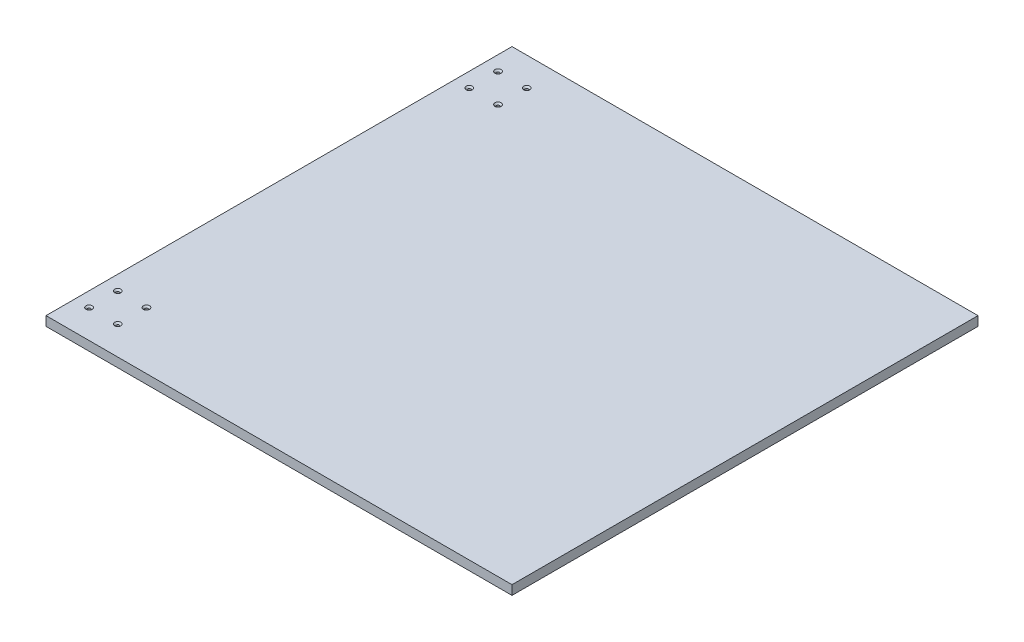
SolidWorks part; units mm, degrees
material "Buk"
ref_plane "Płaszczyzna przednia" through (0, 0, 0) normal (0, 0, 1) x (1, 0, 0)
ref_plane "Płaszczyzna górna" through (0, 0, 0) normal (0, 1, 0) x (1, 0, 0)
ref_plane "Płaszczyzna prawa" through (0, 0, 0) normal (1, 0, 0) x (0, 0, -1)
sketch "Szkic1" plane through (0, 0, 0) normal (0, 1, 0) x (1, 0, 0)
  line L1 (0, 0) -> (500, 0)
  line L2 (0, 0) -> (0, 500)
  line L3 (0, 500) -> (500, 500)
  line L4 (500, 0) -> (500, 500)
  dimension "D1" = 500
extrude "Dodanie-wyciągnięcie1" add sketch "Szkic1" along normal blind 10
sketch "Szkic2" plane through (0, 10, 0) normal (0, 1, 0) x (1, 0, 0)
  line L0 (0, 0) -> (500, 0) construction
  line L1 (0, 500) -> (0, 0) construction
  line L2 (0, 250) -> (500, 250) construction
  line L3 (500, 0) -> (500, 500) construction
  circle A0 centre (15.6, 30.6) radius 1.6
  circle A1 centre (15.6, 61.4) radius 1.6
  circle A2 centre (46.4, 61.4) radius 1.6
  circle A3 centre (46.4, 30.6) radius 1.6
  circle A4 centre (15.6, 438.6) radius 1.6
  circle A5 centre (15.6, 469.4) radius 1.6
  circle A6 centre (46.4, 469.4) radius 1.6
  circle A7 centre (46.4, 438.6) radius 1.6
  dimension "D1" = 3.2
  dimension "D2" = 3.2
  dimension "D3" = 3.2
  dimension "D4" = 3.2
  dimension "D5" = 30.6
  dimension "D6" = 30.6
  dimension "D7" = 30.8
  dimension "D8" = 15.6
  dimension "D9" = 15.6
  dimension "D10" = 30.8
  dimension "D11" = 30.8
  dimension "D12" = 30.8
hole_wizard "Pogłębienie stożkowe pod M3 Wkręt ustalający1" positions "Szkic3" profile "Szkic5" countersink size "M3" standard "Ansi Metric"
sketch "Szkic3" plane through (0, 10, 0) normal (0, 1, 0) x (1, 0, 0)
  point P0 (46.4, 30.6)
  point P3 (46.4, 61.4)
  point P6 (15.6, 61.4)
  point P9 (15.6, 30.6)
  point P12 (46.4, 438.6)
  point P15 (46.4, 469.4)
  point P18 (15.6, 469.4)
  point P21 (15.6, 438.6)
sketch "Szkic5" plane through (46.4, 10, -30.6) normal (1, 0, 0) x (0, 0, 1)
  line L0 (0, 0) -> (0, 11.0215)
  line L1 (0, 11.0215) -> (1.7, 10)
  line L2 (1.7, 10) -> (1.7, 1.66)
  line L3 (1.7, 1.66) -> (3.36, 0)
  line L5 (3.36, 0) -> (0, 0)
  line L6 (-1.7, 1.66) -> (-3.36, 0) construction
  line L10 (0, 11.0215) -> (-1.7, 10) construction
  line L11 (0, -6.35) -> (0, 107.95) construction
  dimension "Œrednica otworu" = 3.4
  dimension "G³êbokoœc otworu" = 10
  dimension "Œrednica zewnêtrznego pog³êbienia sto¿kowego" = 6.72
  dimension "K¹t zewnêtrznego pog³êbienia sto¿kowego" = 90
  dimension "K¹t wiert³a" = 118
